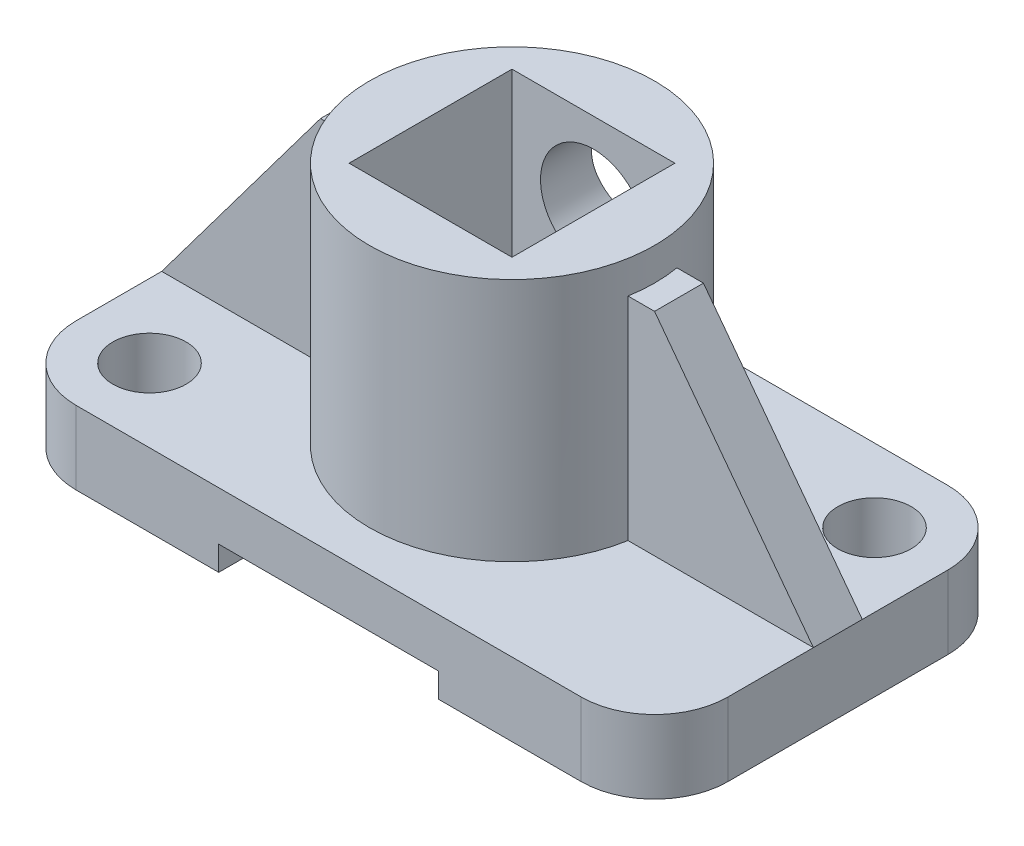
SolidWorks part; units mm, degrees
ref_plane "前视基准面" through (0, 0, 0) normal (0, 0, 1) x (1, 0, 0)
ref_plane "上视基准面" through (0, 0, 0) normal (0, 1, 0) x (1, 0, 0)
ref_plane "右视基准面" through (0, 0, 0) normal (1, 0, 0) x (0, 0, -1)
other "Configuration Table"
sketch "草图1" plane through (0, 0, 0) normal (0, 1, 0) x (1, 0, 0)
  line L0 (0, -90) -> (376.6154, -90) construction
  line L1 (0, 0) -> (320, 0)
  line L2 (0, 0) -> (0, -180)
  line L3 (0, -180) -> (320, -180)
  line L4 (320, 0) -> (320, -180)
  line L5 (160, 0) -> (160, -275.9385) construction
  circle A0 centre (36, -36) radius 18
  circle A1 centre (36, -144) radius 18
  circle A2 centre (284, -36) radius 18
  circle A3 centre (284, -144) radius 18
  circle A4 centre (36, -144) radius 36
  circle A5 centre (36, -36) radius 36
  circle A6 centre (284, -144) radius 36
  circle A7 centre (284, -36) radius 36
  dimension "D4" = 36
  dimension "D1" = 320
  dimension "D2" = 180
  dimension "D3" = 54
  dimension "D5" = 54
  dimension "D6" = 124
extrude "凸台-拉伸1" add sketch "草图1" along normal blind 36 contours A5 A0 | L4 A7 L1 A5 L2 A4 L3 A6 | A4 A1 | A7 A2 | A6 A3 | A3 region at (160, 0, 90) region at (60.7358, 0, 11.2642) region at (308.7358, 0, 11.2642) region at (36, 0, 109.0182) region at (308.7358, 0, 168.7358)
ref_plane "基准面1" through (0, 0, 90) normal (0, 0, 1) x (1, 0, 0)
sketch "草图2" plane through (0, 36, 0) normal (0, 1, 0) x (1, 0, 0)
  line L0 (36, 0) -> (284, 0) construction
  line L1 (160, 0) -> (160, -90)
  line L2 (0, -90) -> (325.126, -90)
  line L3 (0, -36) -> (0, -144) construction
  line L4 (-164.2141, -90) -> (164.2141, -90) construction
  line L6 (120, -50) -> (200, -50)
  line L7 (120, -50) -> (120, -130)
  line L8 (120, -130) -> (200, -130)
  line L9 (200, -50) -> (200, -130)
  line L10 (120, -50) -> (200, -130) construction
  line L11 (120, -130) -> (200, -50) construction
  circle A0 centre (160, -90) radius 70
  dimension "D1" = 140
  dimension "D2" = 80
  dimension "D3" = 80
extrude "凸台-拉伸2" add sketch "草图2" along normal blind 120 contours L1 A0 L2 L7 L6 | L2 A0 L9 L8 L7 | L2 A0 L1 L6 L9 | L7 L6 L9 L8 region at (208.7975, 36, 41.2025) region at (159.0101, 36, 35) region at (160, 36, 158.4348)
extrude "切除-拉伸1" cut sketch "草图2<3>" against normal blind 100 from offset 120 contours L9 L6 L1 L2 | L6 L7 L2 L1 | L7 L6 L9 L8 region at (180, 36, 70) region at (140, 36, 70)
sketch "草图2<3>" plane through (0, 36, 0) normal (0, 1, 0) x (1, 0, 0) same geometry as "草图2"
sketch "草图5" plane through (0, 56, 0) normal (0, 1, 0) x (1, 0, 0)
  line L1 (160, -50) -> (160, -173.2562) construction
  line L2 (120, -50) -> (200, -50) construction
  line L3 (-164.2141, -90) -> (164.2141, -90) construction
  circle A0 centre (160, -90) radius 26
  dimension "D1" = 52
extrude "切除-拉伸2" cut sketch "草图5" against normal through all
sketch "草图6" plane through (0, 0, 0) normal (0, 0, -1) x (-1, 0, 0)
  line L0 (-214, 0) -> (-106, 0)
  line L1 (-36, 0) -> (-284, 0)
  line L2 (-36, 0) -> (-284, 0) construction
  line L3 (-160, 0) -> (-160, 235.0963) construction
  line L4 (-106, 0) -> (-106, 12)
  line L5 (-106, 12) -> (-214, 12)
  line L6 (-214, 0) -> (-214, 12)
  point P9 (-160, 12)
  line M6 (-284, 0) -> (-36, 0)
  dimension "D1" = 54
  dimension "D2" = 12
extrude "切除-拉伸3" cut sketch "草图6" against normal through all contours L3 L5 L6 M6 | L3 L1 L4 L5 region at (187, 6, 0) region at (133, 6, 0)
sketch "草图7" plane through (0, 0, 0) normal (0, 0, -1) x (-1, 0, 0)
  line L1 (-160, 156) -> (-160, 36.2746)
  line L2 (-90, 156) -> (-230, 156) construction
  circle A0 centre (-160, 116) radius 26
  dimension "D1" = 52
  dimension "D2" = 40
extrude "切除-拉伸4" cut sketch "草图7" against normal up to surface (50 mm away) contours L1 A0 | L1 A0 region at (148.9653, 116, 0) region at (171.0347, 116, 0) up to face at (160, 106, 50)
sketch "草图8" plane through (0, 0, 90) normal (0, 0, 1) x (1, 0, 0)
  line L0 (320, 36) -> (242, 36)
  line L1 (36, 36) -> (284, 36) construction
  line L2 (242, 36) -> (242, 140)
  line L3 (242, 140) -> (230, 140)
  line L4 (230, 36) -> (230, 156) construction
  line L5 (242, 140) -> (320, 36)
  line L6 (230, 140) -> (230, 36)
  line L7 (230, 36) -> (242, 36)
  line L8 (160, 36) -> (160, 196.89) construction
  line L9 (90, 36) -> (78, 36)
  line L10 (78, 140) -> (90, 140)
  line L11 (90, 140) -> (90, 36)
  line L12 (78, 36) -> (78, 140)
  line L13 (0, 36) -> (78, 36)
  line L14 (78, 140) -> (0, 36)
  dimension "D1" = 12
  dimension "D2" = 104
extrude "凸台-拉伸4" add sketch "草图8" along normal mid plane 24 separate body contours L12 L14 L13 | L12 L9 L11 L10 | L6 L7 L2 L3 | L5 L2 L0 region at (268, 70.6667, 90) region at (236, 88, 90) region at (84, 88, 90) region at (52, 70.6667, 90)
sketch "草图9" plane through (230, 0, 0) normal (-1, 0, 0) x (0, 0, 1)
  line L4 (78, 140) -> (78, 36)
  line L5 (78, 36) -> (102, 36)
  line L6 (102, 36) -> (102, 140)
  line L7 (102, 140) -> (78, 140)
  line L8 (78, 140) -> (78, 36)
  line L9 (78, 36) -> (102, 36)
  line L10 (102, 36) -> (102, 140)
  line L11 (102, 140) -> (78, 140)
  dimension "D1" = 0
extrude "凸台-拉伸5" add sketch "草图9" along normal blind 18
sketch "草图10" plane through (90, 0, 0) normal (1, 0, 0) x (0, 0, -1)
  line L4 (-78, 36) -> (-78, 140)
  line L5 (-78, 140) -> (-102, 140)
  line L6 (-102, 140) -> (-102, 36)
  line L7 (-102, 36) -> (-78, 36)
  line L8 (-78, 36) -> (-78, 140)
  line L9 (-78, 140) -> (-102, 140)
  line L10 (-102, 140) -> (-102, 36)
  line L11 (-102, 36) -> (-78, 36)
  dimension "D1" = 0
extrude "凸台-拉伸6" add sketch "草图10" along normal blind 18
